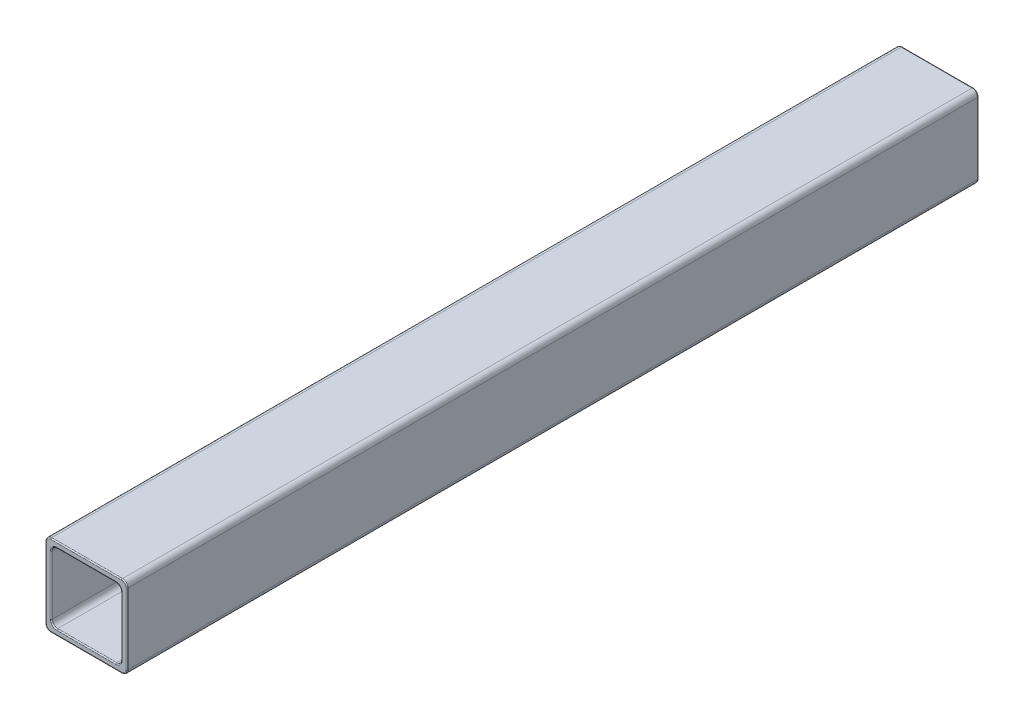
SolidWorks part; units mm, degrees
material "ASTM A500 Grade B Steel"
ref_plane "Front Plane" through (0, 0, 0) normal (0, 0, 1) x (1, 0, 0)
ref_plane "Top Plane" through (0, 0, 0) normal (0, 1, 0) x (1, 0, 0)
ref_plane "Right Plane" through (0, 0, 0) normal (1, 0, 0) x (0, 0, -1)
sketch "Sketch1" plane through (0, 0, 0) normal (0, 0, 1) x (1, 0, 0)
  line L0 (5.3086, -2.7686) -> (32.7914, -2.7686)
  line L1 (2.54, 0) -> (35.56, 0)
  line L2 (0, -2.54) -> (0, -35.56)
  line L3 (2.54, -38.1) -> (35.56, -38.1)
  line L4 (38.1, -2.54) -> (38.1, -35.56)
  line L5 (35.3314, -5.3086) -> (35.3314, -32.7914)
  line L6 (5.3086, -35.3314) -> (32.7914, -35.3314)
  line L7 (2.7686, -5.3086) -> (2.7686, -32.7914)
  line L8 (0, 0) -> (0, -38.1) construction
  line L9 (0, -38.1) -> (38.1, -38.1) construction
  line L10 (38.1, 0) -> (38.1, -38.1) construction
  line L11 (2.7686, -2.7686) -> (2.7686, -35.3314) construction
  line L12 (2.7686, -35.3314) -> (35.3314, -35.3314) construction
  line L13 (35.3314, -2.7686) -> (35.3314, -35.3314) construction
  line L14 (2.7686, -2.7686) -> (35.3314, -2.7686) construction
  line L15 (0, 0) -> (38.1, 0) construction
  arc A0 (0, -35.56) -> (2.54, -38.1) centre (2.54, -35.56) ccw
  arc A1 (38.1, -35.56) -> (35.56, -38.1) centre (35.56, -35.56) cw
  arc A2 (2.7686, -32.7914) -> (5.3086, -35.3314) centre (5.3086, -32.7914) ccw
  arc A3 (32.7914, -35.3314) -> (35.3314, -32.7914) centre (32.7914, -32.7914) ccw
  arc A4 (35.3314, -5.3086) -> (32.7914, -2.7686) centre (32.7914, -5.3086) ccw
  arc A5 (38.1, -2.54) -> (35.56, 0) centre (35.56, -2.54) ccw
  arc A6 (0, -2.54) -> (2.54, 0) centre (2.54, -2.54) cw
  arc A7 (5.3086, -2.7686) -> (2.7686, -5.3086) centre (5.3086, -5.3086) ccw
  point P12 (0, -38.1)
  dimension "D4" = 2.54
  dimension "D3" = 2.7686
extrude "Boss-Extrude1" add sketch "Sketch1" along normal blind 397
sketch "Sketch2" plane through (0, 0, 0) normal (0, 0, -1) x (-1, 0, 0)
  line L4 (0, -35.56) -> (0, -2.54)
  line L5 (-2.54, 0) -> (-35.56, 0)
  line L6 (-38.1, -2.54) -> (-38.1, -35.56)
  line L7 (-35.56, -38.1) -> (-2.54, -38.1)
  line L8 (0, -35.56) -> (0, -2.54)
  line L9 (-2.54, 0) -> (-35.56, 0)
  line L10 (-38.1, -2.54) -> (-38.1, -35.56)
  line L11 (-35.56, -38.1) -> (-2.54, -38.1)
  arc A4 (-2.54, -38.1) -> (0, -35.56) centre (-2.54, -35.56) ccw
  arc A5 (0, -2.54) -> (-2.54, 0) centre (-2.54, -2.54) ccw
  arc A6 (-35.56, 0) -> (-38.1, -2.54) centre (-35.56, -2.54) ccw
  arc A7 (-38.1, -35.56) -> (-35.56, -38.1) centre (-35.56, -35.56) ccw
  arc A8 (-2.54, -38.1) -> (0, -35.56) centre (-2.54, -35.56) ccw
  arc A9 (0, -2.54) -> (-2.54, 0) centre (-2.54, -2.54) ccw
  arc A10 (-35.56, 0) -> (-38.1, -2.54) centre (-35.56, -2.54) ccw
  arc A11 (-38.1, -35.56) -> (-35.56, -38.1) centre (-35.56, -35.56) ccw
  dimension "D1" = 0
extrude "Boss-Extrude2" [suppressed] add sketch "Sketch2" along normal up to surface (0.6787 mm away)
fillet "Fillet1" radius 0.5 32 edges at (34.5875, -3.5125, 397) (35.3314, -19.05, 397) (34.5875, -34.5875, 397) (19.05, -35.3314, 397) (3.5125, -34.5875, 397) (2.7686, -19.05, 397) (3.5125, -3.5125, 397) (37.3561, -0.7439, 397) (38.1, -19.05, 397) (37.3561, -37.3561, 397) (19.05, -38.1, 397) (0.7439, -37.3561, 397) (0, -19.05, 397) (0.7439, -0.7439, 397) (37.3561, -0.7439, 0) (38.1, -19.05, 0) (37.3561, -37.3561, 0) (19.05, -38.1, 0) (0.7439, -37.3561, 0) (0, -19.05, 0) (0.7439, -0.7439, 0) (34.5875, -3.5125, 0) (35.3314, -19.05, 0) (34.5875, -34.5875, 0) (19.05, -35.3314, 0) (3.5125, -34.5875, 0) (2.7686, -19.05, 0) (3.5125, -3.5125, 0) (19.05, -2.7686, 397) (19.05, 0, 397) (19.05, 0, 0) (19.05, -2.7686, 0)
